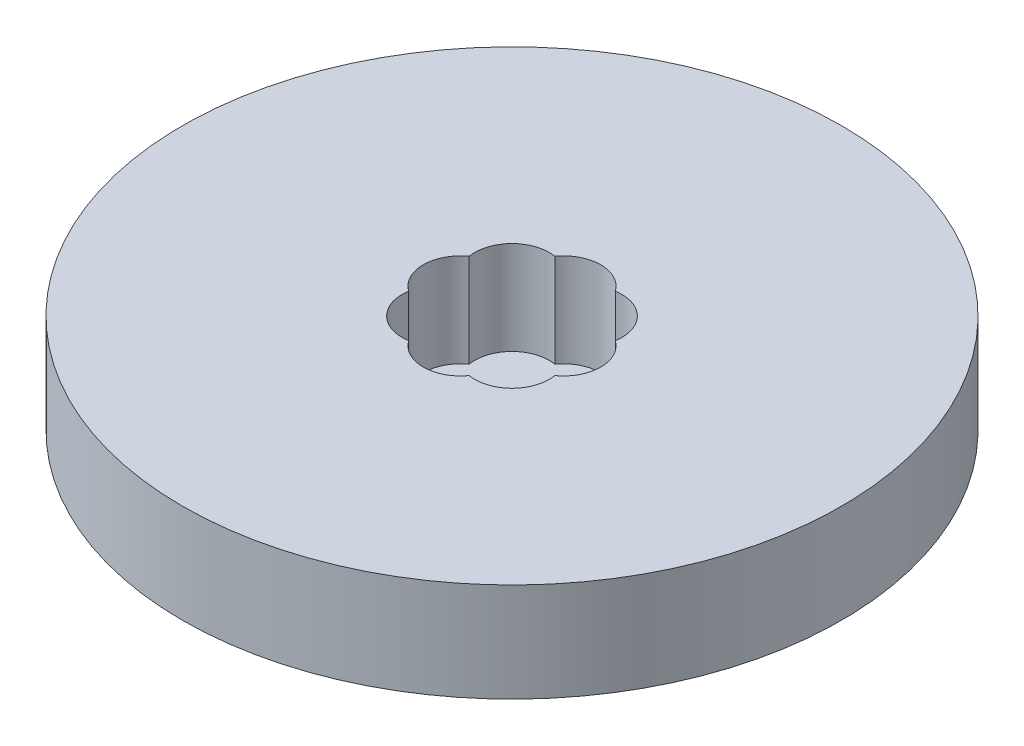
SolidWorks part; units mm, degrees
ref_plane "Front Plane" through (0, 0, 0) normal (0, 0, 1) x (1, 0, 0)
ref_plane "Top Plane" through (0, 0, 0) normal (0, 1, 0) x (1, 0, 0)
ref_plane "Right Plane" through (0, 0, 0) normal (1, 0, 0) x (0, 0, -1)
sketch "Sketch1" plane through (0, 0, 0) normal (0, 1, 0) x (1, 0, 0)
  circle A0 centre (0, 0) radius 80
  dimension "FLANGE_OD" = 160
extrude "Boss-Extrude1" add sketch "Sketch1" along normal blind 24
sketch "Sketch2" plane through (0, 0, 0) normal (0, 1, 0) x (1, 0, 0)
  circle A0 centre (0, 0) radius 7.5
  dimension "BORE_D" = 15
extrude "Cut-Extrude1" cut sketch "Sketch2" along normal through all
sketch "Sketch3" plane through (0, 24, 0) normal (0, 1, 0) x (1, 0, 0)
  circle A0 centre (0, 0) radius 12.499 construction
  circle A1 centre (-12.499, 0) radius 9.0271
  dimension "BOLT_D" = 18.0542
  dimension "BOLT_PCD" = 24.998
extrude "Cut-Extrude2" cut sketch "Sketch3" against normal blind 22.6918
pattern_circular "CirPattern1" count 8 over 360 about axis through (0, 0, 0) along (0, 1, 0) of "Cut-Extrude2"
